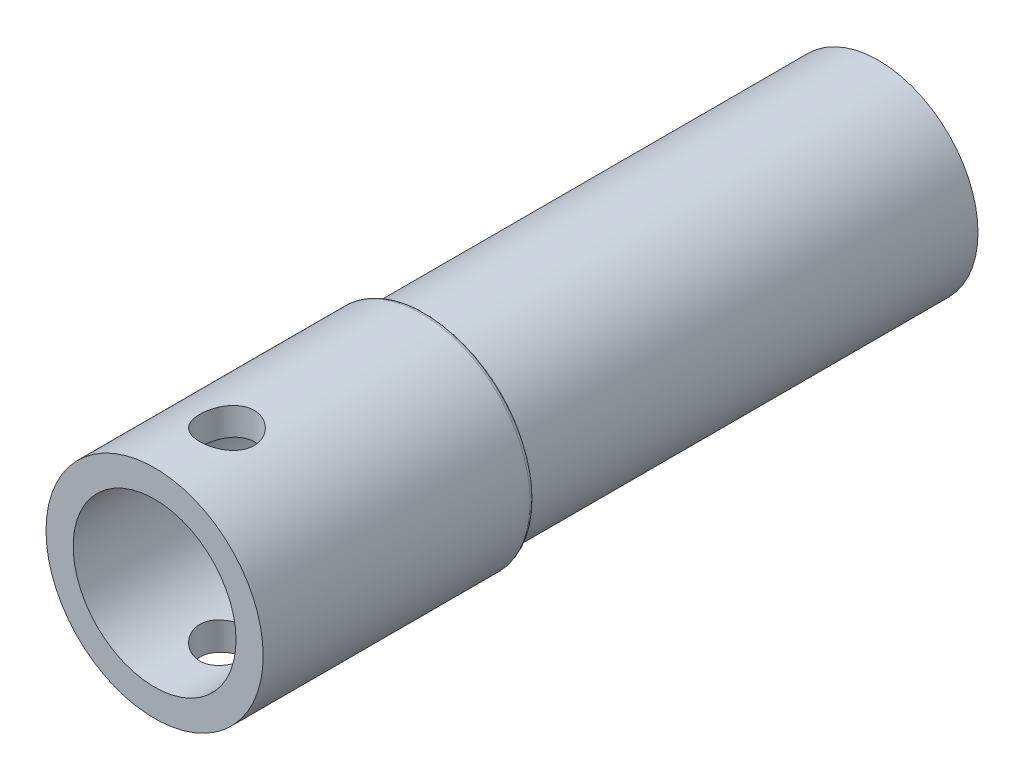
SolidWorks part; units mm, degrees
ref_plane "Front Plane" through (0, 0, 0) normal (0, 0, 1) x (1, 0, 0)
ref_plane "Top Plane" through (0, 0, 0) normal (0, 1, 0) x (1, 0, 0)
ref_plane "Right Plane" through (0, 0, 0) normal (1, 0, 0) x (0, 0, -1)
sketch "Sketch1" plane through (0, 0, 0) normal (0, 0, 1) x (1, 0, 0)
  circle A5 centre (0, 0) radius 9
  circle A6 centre (0, 0) radius 12
  dimension "D1" = 18
  dimension "D2" = 24
extrude "Boss-Extrude1" add sketch "Sketch1" along normal blind 30
sketch "Sketch2" plane through (0, 0, 0) normal (0, 0, -1) x (-1, 0, 0)
  circle A2 centre (0, 0) radius 11
  dimension "D1" = 22
extrude "Boss-Extrude2" add sketch "Sketch2" along normal blind 50
sketch "Sketch3" plane through (0, 0, -50) normal (0, 0, -1) x (-1, 0, 0)
  circle A0 centre (0, 0) radius 5
  dimension "D1" = 10
extrude "Cut-Extrude1" cut sketch "Sketch3" against normal blind 40
sketch "Sketch4" plane through (0, 0, 0) normal (0, 1, 0) x (1, 0, 0)
  line L1 (-12, -30) -> (12, -30) construction
  circle A0 centre (0, -22) radius 3
  dimension "D1" = 6
  dimension "D2" = 8
extrude "Cut-Extrude2" cut sketch "Sketch4" against normal through all and the other way through all
ref_plane "Plane1" through (0, 0, 22) normal (0, 0, -1) x (-1, 0, 0)
ref_plane "Plane2" through (0, 0, 22) normal (0, 0, -1) x (-1, 0, 0)
ref_plane "Plane3" through (0, 0, 22) normal (0, 0, -1) x (-1, 0, 0)
fillet "Fillet1" radius 0.5 2 edges at (12, 0, 0) (-11, 0, 0)
